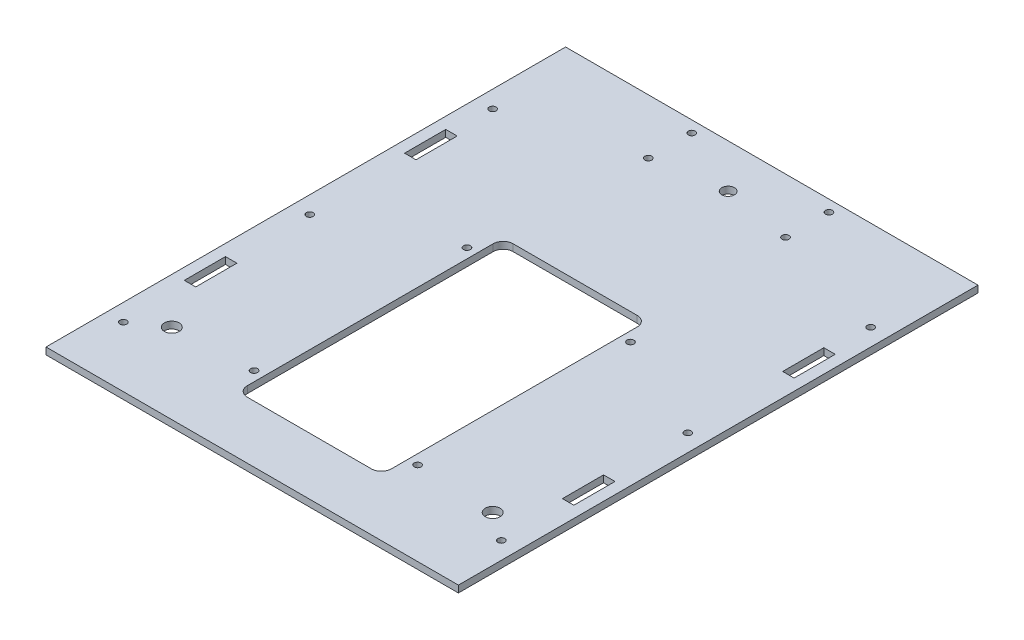
SolidWorks part; units mm, degrees
material "PMMA"
ref_plane "Front Plane" through (0, 0, 0) normal (0, 0, 1) x (1, 0, 0)
ref_plane "Top Plane" through (0, 0, 0) normal (0, 1, 0) x (1, 0, 0)
ref_plane "Right Plane" through (0, 0, 0) normal (1, 0, 0) x (0, 0, -1)
sketch "Schizzo1" plane through (0, 0, 0) normal (0, 1, 0) x (1, 0, 0)
  line L0 (90.17, 113.61) -> (-90.17, -113.61) construction
  line L1 (-90.17, 113.61) -> (90.17, 113.61)
  line L2 (-90.17, 113.61) -> (-90.17, -113.61)
  line L3 (-90.17, -113.61) -> (90.17, -113.61)
  line L4 (90.17, 113.61) -> (90.17, -113.61)
  point P4 (0, 0)
  dimension "D1" = 227.22
  dimension "D2" = 180.34
extrude "Estrusione-Estrusione1" add sketch "Schizzo1" along normal blind 3
sketch "Schizzo3" plane through (0, 0, 0) normal (0, 1, 0) x (1, 0, 0)
  line L0 (0, 113.61) -> (0, -113.61) construction
  line L1 (-31.5, -88.61) -> (-31.5, 27.62) construction
  line L2 (-31.5, -88.61) -> (31.5, -88.61) construction
  line L3 (31.5, -88.61) -> (31.5, 27.62) construction
  line L4 (-31.5, 27.62) -> (31.5, 27.62) construction
  line L5 (90.17, 113.61) -> (-90.17, 113.61) construction
  line L6 (-90.17, -113.61) -> (90.17, -113.61) construction
  line L7 (-31.5, -84.26) -> (-31.5, 23.27)
  line L8 (-27.15, -88.61) -> (27.15, -88.61)
  line L9 (31.5, -84.26) -> (31.5, 23.27)
  line L10 (-27.15, 27.62) -> (27.15, 27.62)
  line L11 (-35.75, -77.045) -> (35.75, -77.045) construction
  line L12 (0, 27.62) -> (0, -88.61) construction
  line L13 (-35.75, 16.055) -> (-35.75, -77.045) construction
  line L14 (-35.75, 16.055) -> (35.75, 16.055) construction
  line L15 (35.75, -77.045) -> (35.75, 16.055) construction
  arc A0 (-31.5, -84.26) -> (-27.15, -88.61) centre (-27.15, -84.26) ccw
  arc A1 (31.5, -84.26) -> (27.15, -88.61) centre (27.15, -84.26) cw
  arc A2 (27.15, 27.62) -> (31.5, 23.27) centre (27.15, 23.27) cw
  arc A3 (-31.5, 23.27) -> (-27.15, 27.62) centre (-27.15, 23.27) cw
  circle A4 centre (-35.75, -77.045) radius 1.5
  circle A5 centre (35.75, -77.045) radius 1.5
  circle A6 centre (-35.75, 16.055) radius 1.5
  circle A7 centre (35.75, 16.055) radius 1.5
  point P29 (0, -77.045)
  dimension "D12" = 3
  dimension "D1" = 116.23
  dimension "D2" = 63
  dimension "D4" = 4.35
  dimension "D5" = 4.35
  dimension "D6" = 4.35
  dimension "D7" = 4.35
  dimension "D8" = 4.35
  dimension "D9" = 4.35
  dimension "D10" = 4.35
  dimension "D11" = 4.35
  dimension "D13" = 71.5
  dimension "D14" = 93.1
  dimension "D3" = 25
  dimension "D15" = 116.23
  dimension "D16" = 11.565
  dimension "D17" = 11.565
sketch "Schizzo2" plane through (0, 0, 0) normal (0, 1, 0) x (1, 0, 0)
  line L0 (90.17, -113.61) -> (90.17, 113.61) construction
  line L1 (85.17, -40.13) -> (80.17, -40.13)
  line L2 (85.17, -40.13) -> (85.17, -58.13)
  line L3 (85.17, -58.13) -> (80.17, -58.13)
  line L4 (80.17, -40.13) -> (80.17, -58.13)
  line L5 (-90.17, -113.61) -> (90.17, -113.61) construction
  line L6 (0, -113.61) -> (0, 113.61) construction
  line L7 (90.17, 113.61) -> (-90.17, 113.61) construction
  line L8 (-85.17, -40.13) -> (-80.17, -40.13)
  line L9 (-85.17, -40.13) -> (-85.17, -58.13)
  line L10 (-85.17, -58.13) -> (-80.17, -58.13)
  line L11 (-80.17, -40.13) -> (-80.17, -58.13)
  line L12 (-82.67, 113.61) -> (-82.67, -113.61) construction
  line L13 (-90.17, -78.61) -> (90.17, -78.61) construction
  line L14 (-85.17, 38.19) -> (-80.17, 38.19)
  line L15 (-85.17, 38.19) -> (-85.17, 56.19)
  line L16 (-85.17, 56.19) -> (-80.17, 56.19)
  line L17 (-80.17, 38.19) -> (-80.17, 56.19)
  line L18 (85.17, 38.19) -> (80.17, 38.19)
  line L19 (80.17, 38.19) -> (80.17, 56.19)
  line L20 (85.17, 56.19) -> (80.17, 56.19)
  line L21 (85.17, 38.19) -> (85.17, 56.19)
  line L22 (0, 103.9337) -> (0, 44.5482) construction
  line L23 (-90.17, 113.61) -> (-90.17, -113.61) construction
  circle A0 centre (-82.67, -5.81) radius 1.5
  circle A1 centre (-82.67, -87.31) radius 1.5
  circle A2 centre (-82.67, 74.19) radius 1.5
  circle A3 centre (82.67, -87.31) radius 1.5
  circle A4 centre (82.67, -5.81) radius 1.5
  circle A5 centre (82.67, 74.19) radius 1.5
  circle A6 centre (-70.17, -78.61) radius 3.25
  circle A7 centre (70.17, -78.61) radius 3.25
  circle A8 centre (-30, 89.61) radius 1.5
  circle A9 centre (-30, 108.61) radius 1.5
  circle A10 centre (30, 89.61) radius 1.5
  circle A11 centre (30, 108.61) radius 1.5
  circle A12 centre (0, 94.51) radius 2.75
  point P18 (-82.67, -58.13)
  dimension "D6" = 3
  dimension "D11" = 6.5
  dimension "D13" = 3
  dimension "D17" = 5.5
  dimension "D2" = 5
  dimension "D4" = 18
  dimension "D3" = 55.48
  dimension "D5" = 57.42
  dimension "D7" = 26.3
  dimension "D8" = 107.8
  dimension "D9" = 187.8
  dimension "D10" = 35
  dimension "D12" = 20
  dimension "D14" = 30
  dimension "D15" = 19
  dimension "D16" = 5
  dimension "D18" = 19.1
extrude "Taglio-Estrusione1" cut sketch "Schizzo2" along direction (0, 1, 0) on the side of the normal through all
extrude "Taglio-Estrusione5" cut sketch "Schizzo3" along direction (0, 1, 0) on the side of the normal through all
equation "\"Thickness5\"=5"
equation "\"D1@Estrusione-Estrusione1\"=\"Thickness3\""
equation "\"D1@Schizzo2\"=\"Thickness5\""
equation "\"D2@Schizzo2\"=\"Thickness5\""
equation "\"Thickness3\"=3"
equation "\"D5@Schizzo3\"=\"D4@Schizzo3\""
equation "\"D6@Schizzo3\"=\"D5@Schizzo3\""
equation "\"D7@Schizzo3\"=\"D6@Schizzo3\""
equation "\"D8@Schizzo3\"=\"D7@Schizzo3\""
equation "\"D9@Schizzo3\"=\"D8@Schizzo3\""
equation "\"D10@Schizzo3\"=\"D9@Schizzo3\""
equation "\"D11@Schizzo3\"=\"D10@Schizzo3\""
